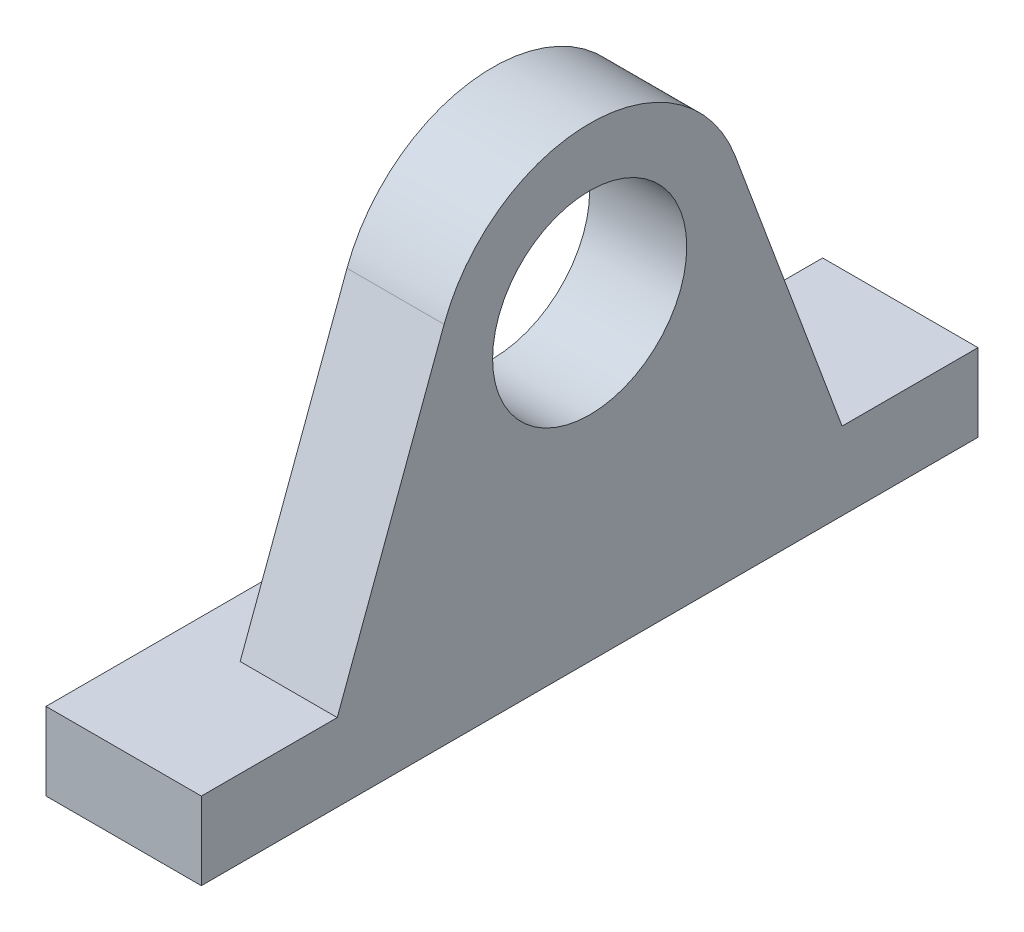
SolidWorks part; units mm, degrees
ref_plane "前视基准面" through (0, 0, 0) normal (0, 0, 1) x (1, 0, 0)
ref_plane "上视基准面" through (0, 0, 0) normal (0, 1, 0) x (1, 0, 0)
ref_plane "右视基准面" through (0, 0, 0) normal (1, 0, 0) x (0, 0, -1)
sketch "草图1" plane through (0, 0, 0) normal (1, 0, 0) x (0, 0, -1)
  line L0 (0, 0) -> (0, 51.6076) construction
  line L1 (-7.4979, 18.7894) -> (-13, 4)
  line L2 (-13, 4) -> (-20, 4)
  line L3 (-20, 4) -> (-20, 0)
  line L4 (-20, 0) -> (20, 0)
  line L5 (20, 0) -> (20, 4)
  line L6 (20, 4) -> (13, 4)
  line L7 (13, 4) -> (7.4979, 18.7894)
  arc A0 (7.4979, 18.7894) -> (-7.4979, 18.7894) centre (0, 16) ccw
  circle A1 centre (0, 16) radius 5
  dimension "D1" = 10
  dimension "D2" = 16
  dimension "D3" = 40
  dimension "D4" = 7
  dimension "D5" = 4
  dimension "D6" = 16
extrude "凸台-拉伸1" add sketch "草图1" along normal blind 5
sketch "草图2" plane through (0, 4, 0) normal (0, 1, 0) x (1, 0, 0)
  line L1 (0, 20) -> (-3, 20)
  line L2 (0, 20) -> (0, -20)
  line L3 (0, -20) -> (-3, -20)
  line L4 (-3, 20) -> (-3, -20)
  line L5 (5, -20) -> (0, -20) construction
  point P4 (0, 0)
  point P14 (0, 0)
  point P15 (0, 0)
  point P17 (0, 0)
  dimension "D1" = 3
extrude "凸台-拉伸2" add sketch "草图2" against normal up to surface (4 mm away) up to face at (2.5, 0, 0)
